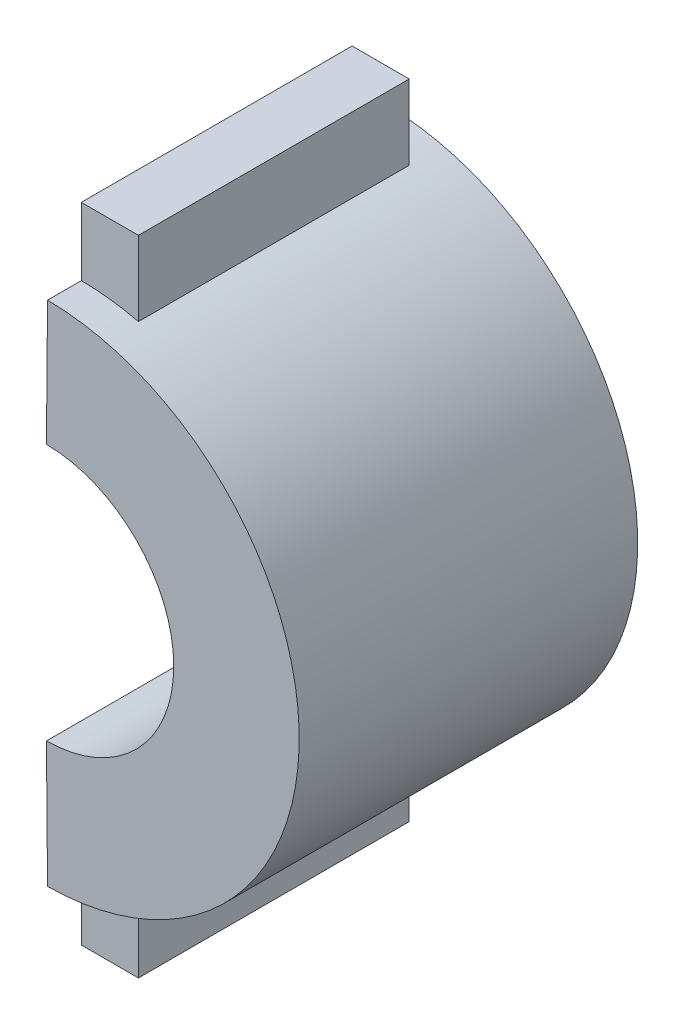
SolidWorks part; units mm, degrees
material "AISI Type 316L stainless steel"
ref_plane "Front Plane" through (0, 0, 0) normal (0, 0, 1) x (1, 0, 0)
ref_plane "Top Plane" through (0, 0, 0) normal (0, 1, 0) x (1, 0, 0)
ref_plane "Right Plane" through (0, 0, 0) normal (1, 0, 0) x (0, 0, -1)
sketch "Revolve profile 1" plane through (0, 0, 0) normal (0, 1, 0) x (1, 0, 0)
  line L0 (60, 40) -> (60, -40)
  line L1 (60, -40) -> (30.35, -40)
  line L2 (30.35, -40) -> (30.35, 40)
  line L3 (30.35, 40) -> (60, 40)
  line L4 (0, 45) -> (0, -45) construction
  dimension "D1" = 29.65
  dimension "D2" = 60
  dimension "D3" = 80
revolve "Revolve 1" add sketch "Revolve profile 1" angle 179 about L4
move or copy body "Revolve index 1" bodies to move or copy 101 copy no rotation origin (0, 0, 0) rotation axis (0, 0, -1) rotation angle 89.5
sketch "Extrude sketch 1" plane through (0, 0, 0) normal (0, 0, 1) x (1, 0, 0)
  line L0 (14, 56) -> (14, 76)
  line L1 (14, 76) -> (0.5, 76)
  line L2 (0.5, 76) -> (0.5, 56)
  line L3 (0.5, 56) -> (14, 56)
  dimension "D1" = 13.5
  dimension "D2" = 20
extrude "Extrude 1" add sketch "Extrude sketch 1" along normal blind 64 from offset 32 separate body offset against normal yes
sketch "Extrude sketch 2" plane through (0, 0, 0) normal (0, 0, 1) x (1, 0, 0)
  line L0 (14, -76) -> (14, -56)
  line L1 (14, -56) -> (0.5, -56)
  line L2 (0.5, -56) -> (0.5, -76)
  line L3 (0.5, -76) -> (14, -76)
  dimension "D1" = 13.5
  dimension "D2" = 20
extrude "Extrude 2" add sketch "Extrude sketch 2" along normal blind 64 from offset 32 separate body offset against normal yes
combine bodies "Combine (weld / assembly of features)" operation type add bodies to combine 104 103 102
